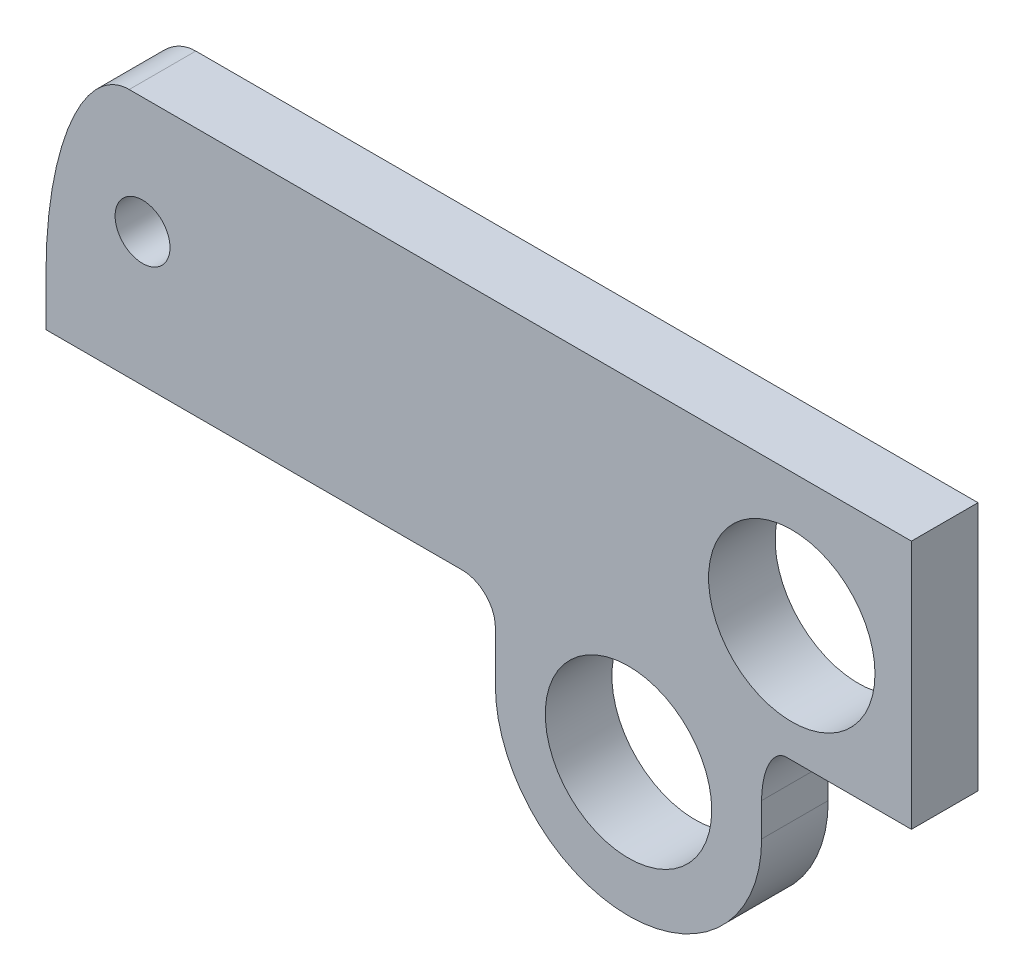
SolidWorks part; units mm, degrees
ref_plane "Plano frontal" through (0, 0, 0) normal (0, 0, 1) x (1, 0, 0)
ref_plane "Plano superior" through (0, 0, 0) normal (0, 1, 0) x (1, 0, 0)
ref_plane "Plano direito" through (0, 0, 0) normal (1, 0, 0) x (0, 0, -1)
sketch "Esboço1" plane through (0, 0, 0) normal (0, 0, 1) x (1, 0, 0)
  line L0 (0, 0) -> (25, 0)
  line L1 (25, 0) -> (25, 28)
  line L3 (-27, 28) -> (-27, 13)
  line L4 (-27, 13) -> (0, 13)
  line L5 (0, 13) -> (0, 0)
  line L10 (-27, 28) -> (25, 28)
  dimension "D1" = 25
  dimension "D2" = 15
  dimension "D3" = 27
  dimension "D4" = 13
extrude "Ressalto-extrusão1" add sketch "Esboço1" along normal blind 4
fillet "Filete3" radius 8 1 edges at (0, 0, 2)
sketch "Esboço2" plane through (0, 0, 4) normal (0, 0, 1) x (1, 0, 0)
  line L0 (-27, 13) -> (0, 13) construction
  line L2 (-27, 28) -> (-27, 13) construction
  line L5 (25, 28) -> (-27, 28) construction
  circle A1 centre (-21.2, 21) radius 1.65
  circle A2 centre (8, 8) radius 5
  circle A3 centre (17.8107, 20) radius 5
  point P15 (9.7525, 30)
  point P16 (-5.442, 30)
  dimension "D1" = 10
  dimension "D2" = 8
  dimension "D4" = 3.3
  dimension "D5" = 5.8
  dimension "D3" = 10
  dimension "D7" = 15.5
  dimension "D8" = 8
extrude "Corte-extrusão1" cut sketch "Esboço2" against normal through all
fillet "Filete12" radius 5 1 edges at (-27, 28, 2) second distance 12 first distance on face at (-1, 28, 2)
fillet "Filete14" radius 2 1 edges at (0, 13, 2)
sketch "Esboço3" plane through (0, 0, 4) normal (0, 0, 1) x (1, 0, 0)
  line L0 (16, 0) -> (16, 13)
  line L1 (8, 0) -> (25, 0) construction
  line L2 (16, 13) -> (25, 13)
  line L3 (25, 0) -> (25, 28) construction
  line L4 (25, 13) -> (25, 0)
  line L5 (25, 0) -> (16, 0)
  dimension "D1" = 9
  dimension "D2" = 13
extrude "Corte-extrusão2" cut sketch "Esboço3" against normal through all contours L2 L4 L5 L0
fillet "Filete15" radius 8 1 edges at (16, 0, 2)
fillet "Filete16" radius 1.5 1 edges at (16, 13, 2) second distance 3 first distance on face at (20.5, 13, 2)
